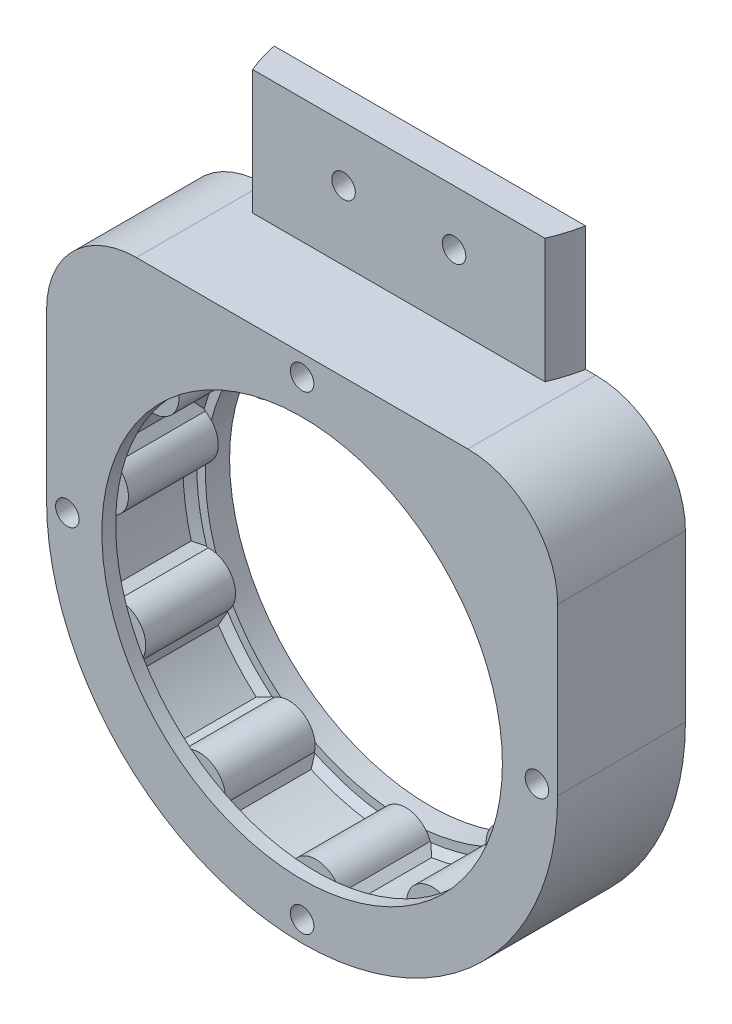
SolidWorks part; units mm, degrees
ref_plane "前视基准面" through (0, 0, 0) normal (0, 0, 1) x (1, 0, 0)
ref_plane "上视基准面" through (0, 0, 0) normal (0, 1, 0) x (1, 0, 0)
ref_plane "右视基准面" through (0, 0, 0) normal (1, 0, 0) x (0, 0, -1)
sketch "草图1" plane through (0, 0, 0) normal (0, 0, 1) x (1, 0, 0)
  line L0 (-37, 0) -> (-37, 24)
  line L1 (37, 0) -> (37, 24)
  line L2 (-24, 37) -> (24, 37)
  arc A0 (-31.2338, 0.6797) -> (-29.7771, -9.4517) centre (0, 0) ccw
  arc A1 (3.7723, -31.0126) -> (-3.7723, -31.0126) centre (0, -31.2412) ccw
  arc A2 (-13.5933, -28.1289) -> (-19.9401, -24.05) centre (-16.8903, -26.2818) ccw
  arc A3 (-26.643, -16.3145) -> (-29.7771, -9.4517) centre (-28.418, -12.9781) ccw
  arc A4 (-31.2338, 0.6797) -> (-30.1601, 8.1474) centre (-30.9232, 4.4461) ccw
  arc A5 (-25.9081, 17.4581) -> (-20.9675, 23.1598) centre (-23.6105, 20.4586) ccw
  arc A6 (-12.3567, 28.6936) -> (-5.1178, 30.8191) centre (-8.8017, 29.9757) ccw
  arc A7 (5.1178, 30.8191) -> (12.3567, 28.6936) centre (8.8017, 29.9757) ccw
  arc A8 (20.9675, 23.1598) -> (25.9081, 17.4581) centre (23.6105, 20.4586) ccw
  arc A9 (30.1601, 8.1474) -> (31.2338, 0.6797) centre (30.9232, 4.4461) ccw
  arc A10 (29.7771, -9.4517) -> (26.643, -16.3145) centre (28.418, -12.9781) ccw
  arc A11 (19.9401, -24.05) -> (13.5933, -28.1289) centre (16.8903, -26.2818) ccw
  arc A12 (-37, 0) -> (37, 0) centre (0, 0) ccw
  arc A13 (-25.9081, 17.4581) -> (-30.1601, 8.1474) centre (0, 0) ccw
  arc A14 (-12.3567, 28.6936) -> (-20.9675, 23.1598) centre (0, 0) ccw
  arc A15 (5.1178, 30.8191) -> (-5.1178, 30.8191) centre (0, 0) ccw
  arc A16 (20.9675, 23.1598) -> (12.3567, 28.6936) centre (0, 0) ccw
  arc A17 (30.1601, 8.1474) -> (25.9081, 17.4581) centre (0, 0) ccw
  arc A18 (29.7771, -9.4517) -> (31.2338, 0.6797) centre (0, 0) ccw
  arc A19 (-26.643, -16.3145) -> (-19.9401, -24.05) centre (0, 0) ccw
  arc A20 (-13.5933, -28.1289) -> (-3.7723, -31.0126) centre (0, 0) ccw
  arc A21 (3.7723, -31.0126) -> (13.5933, -28.1289) centre (0, 0) ccw
  arc A22 (19.9401, -24.05) -> (26.643, -16.3145) centre (0, 0) ccw
  circle A23 centre (0, -34) radius 1.7
  circle A24 centre (-34, 0) radius 1.7
  circle A25 centre (0, 34) radius 1.7
  circle A26 centre (34, 0) radius 1.7
  arc A27 (37, 24) -> (24, 37) centre (24, 24) ccw
  arc A28 (-24, 37) -> (-37, 24) centre (-24, 24) ccw
  point P28 (0, 0)
  point P43 (37.3238, 37.0091)
  point P52 (0, 0)
  point P54 (0, 0)
  dimension "D1" = 11
  dimension "D2" = 34
  dimension "D3" = 4
  dimension "D4" = 13
extrude "凸台-拉伸1" add sketch "草图1" along normal blind 13
sketch "草图2" plane through (0, 0, 13) normal (0, 0, 1) x (1, 0, 0)
  line L0 (-37, 0) -> (-37, 24)
  line L1 (-24, 37) -> (24, 37)
  line L2 (37, 24) -> (37, 0)
  circle A0 centre (0, 0) radius 29
  arc A1 (-37, 0) -> (37, 0) centre (0, 0) ccw
  arc A2 (37, 24) -> (24, 37) centre (24, 24) ccw
  arc A3 (-24, 37) -> (-37, 24) centre (-24, 24) ccw
  dimension "D1" = 13
extrude "凸台-拉伸2" add sketch "草图2" along normal blind 2
sketch "草图3" plane through (0, 0, 0) normal (0, 0, -1) x (-1, 0, 0)
  line L0 (-37, 0) -> (-37, 24)
  line L1 (-24, 37) -> (24, 37)
  line L2 (37, 24) -> (37, 0)
  arc A0 (-37, 0) -> (37, 0) centre (0, 0) ccw
  arc A1 (37, 24) -> (24, 37) centre (24, 24) ccw
  arc A2 (-24, 37) -> (-37, 24) centre (-24, 24) ccw
  circle A3 centre (0, 0) radius 29
  dimension "D1" = 13
extrude "凸台-拉伸3" add sketch "草图3" along normal blind 3.5
chamfer "倒角1" distance 1 angle 45 44 edges at (-19.9401, -24.05, 6.5) (-23.6105, -20.4586, 13) (-26.643, -16.3145, 6.5) (-23.6105, -20.4586, 0) (-3.7723, -31.0126, 6.5) (-8.8017, -29.9757, 13) (-13.5933, -28.1289, 6.5) (-8.8017, -29.9757, 0) (13.5933, -28.1289, 6.5) (8.8017, -29.9757, 13) (3.7723, -31.0126, 6.5) (8.8017, -29.9757, 0) (26.643, -16.3145, 6.5) (23.6105, -20.4586, 13) (19.9401, -24.05, 6.5) (23.6105, -20.4586, 0) (31.2338, 0.6797, 6.5) (30.9232, -4.4461, 13) (29.7771, -9.4517, 6.5) (30.9232, -4.4461, 0) (25.9081, 17.4581, 6.5) (28.418, 12.9781, 13) (30.1601, 8.1474, 6.5) (28.418, 12.9781, 0) (12.3567, 28.6936, 6.5) (16.8903, 26.2818, 13) (20.9675, 23.1598, 6.5) (16.8903, 26.2818, 0) (-5.1178, 30.8191, 6.5) (0, 31.2412, 13) (5.1178, 30.8191, 6.5) (0, 31.2412, 0) (-20.9675, 23.1598, 6.5) (-16.8903, 26.2818, 13) (-12.3567, 28.6936, 6.5) (-16.8903, 26.2818, 0) (-30.1601, 8.1474, 6.5) (-28.418, 12.9781, 13) (-25.9081, 17.4581, 6.5) (-28.418, 12.9781, 0) (-29.7771, -9.4517, 6.5) (-30.9232, -4.4461, 13) (-31.2338, 0.6797, 6.5) (-30.9232, -4.4461, 0)
sketch "草图4" plane through (0, 37, 0) normal (0, 1, 0) x (1, 0, 0)
  line L0 (-22.5555, 3.5) -> (22.5555, 3.5)
  line L2 (0, -1) -> (0, 8) construction
  line L4 (-24, 3.5) -> (24, 3.5) construction
  line L5 (-21.166, -1) -> (21.166, -1)
  circle A0 centre (0, 8) radius 23
  line M6 (24, 3.5) -> (-24, 3.5)
extrude "凸台-拉伸4" add sketch "草图4" along normal blind 18 contours L5 L2 L0 A0 | L2 L5 A0 M6
sketch "草图5" plane through (0, 0, -3.5) normal (0, 0, -1) x (-1, 0, 0)
  line L0 (0, 55) -> (0, 47) construction
  line L1 (-22.5555, 55) -> (22.5555, 55) construction
  line L2 (0, 47) -> (-8, 47) construction
  line L3 (0, 47) -> (8, 47) construction
  circle A0 centre (-8, 47) radius 1.7
  circle A1 centre (8, 47) radius 1.7
  dimension "D1" = 8
extrude "切除-拉伸1" cut sketch "草图5" against normal blind 18
sketch "草图6" plane through (0, 0, 15) normal (0, 0, 1) x (1, 0, 0)
  line L0 (0, 0) -> (0, -34) construction
  circle A0 centre (0, 34) radius 1.7
  circle A1 centre (-34, 0) radius 1.7
  circle A2 centre (0, -34) radius 1.7
  circle A3 centre (34, 0) radius 1.7
extrude "切除-拉伸2" cut sketch "草图6" against normal blind 18.5
